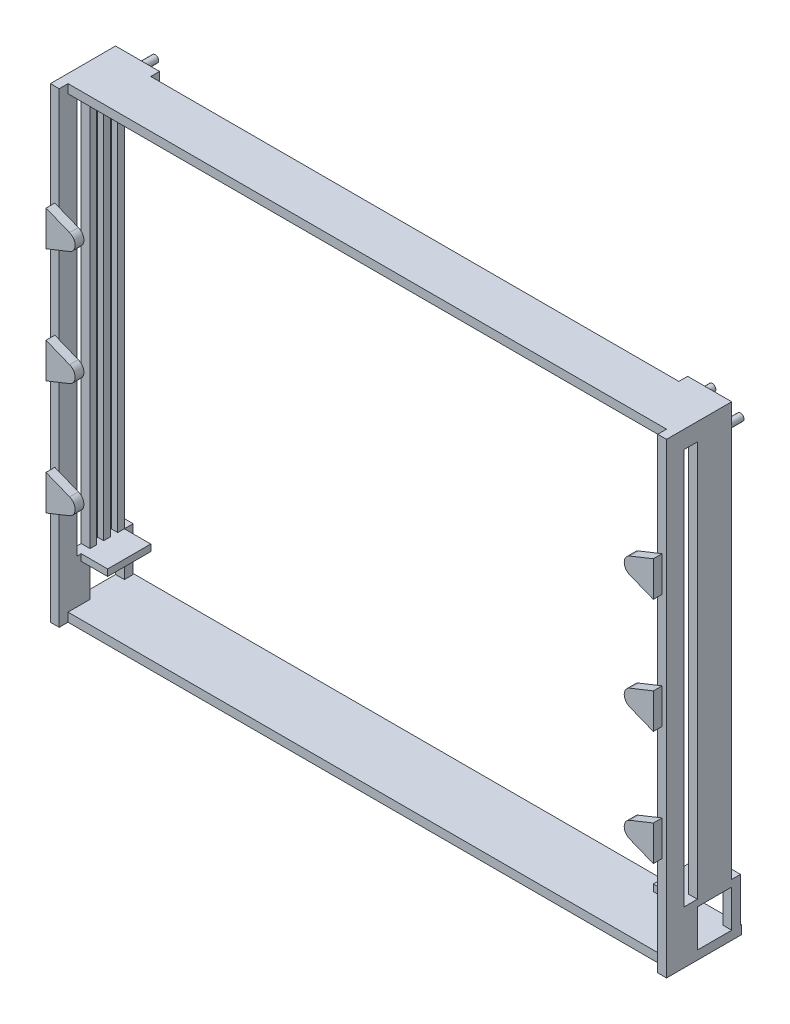
SolidWorks part; units mm, degrees
ref_plane "Plan de face" through (0, 0, 0) normal (0, 0, 1) x (1, 0, 0)
ref_plane "Plan de dessus" through (0, 0, 0) normal (0, 1, 0) x (1, 0, 0)
ref_plane "Plan de droite" through (0, 0, 0) normal (1, 0, 0) x (0, 0, -1)
sketch "Esquisse1" plane through (0, 0, 0) normal (0, 1, 0) x (1, 0, 0)
  line L0 (10, 0) -> (690, 0) construction
  line L1 (0, 0) -> (10, 0)
  line L2 (0, 0) -> (0, 25)
  line L3 (0, 25) -> (10, 25)
  line L4 (10, 0) -> (10, 25)
  line L6 (690, 0) -> (700, 0)
  line L7 (690, 0) -> (690, 25)
  line L8 (690, 25) -> (700, 25)
  line L9 (700, 0) -> (700, 25)
  dimension "D1" = 680
  dimension "D2" = 10
  dimension "D3" = 25
  dimension "D4" = 10
  dimension "D5" = 25
extrude "Boss.-Extru.1" add sketch "Esquisse1" along normal blind 530
sketch "Esquisse7" plane through (0, 0, 0) normal (0, 0, 1) x (1, 0, 0)
  line L0 (5, 530) -> (5, 415) construction
  line L1 (0, 530) -> (10, 530) construction
  line L2 (5, 415) -> (5, 375) construction
  line L3 (5, 375) -> (5, 285) construction
  line L4 (5, 415) -> (55, 395)
  line L5 (55, 395) -> (5, 375)
  line L6 (5, 375) -> (5, 415)
  line L7 (5, 285) -> (5, 245) construction
  line L8 (5, 245) -> (5, 155) construction
  line L9 (5, 155) -> (5, 115) construction
  line L10 (615, 395) -> (5, 395) construction
  line L11 (5, 285) -> (55, 265)
  line L12 (55, 265) -> (5, 245)
  line L13 (5, 245) -> (5, 285)
  line L14 (5, 155) -> (55, 135)
  line L15 (55, 135) -> (5, 115)
  line L16 (5, 115) -> (5, 155)
  line L17 (615, 460) -> (615, 330) construction
  line L18 (615, 330) -> (615, 200) construction
  line L19 (615, 265) -> (5, 265) construction
  line L20 (615, 200) -> (615, 70) construction
  line L21 (615, 135) -> (5, 135) construction
  line L23 (10, 530) -> (690, 530) construction
  line L24 (350, 530) -> (350, 0) construction
  line L25 (85, 135) -> (695, 135) construction
  line L26 (85, 265) -> (695, 265) construction
  line L27 (85, 330) -> (85, 200) construction
  line L28 (85, 395) -> (695, 395) construction
  line L29 (695, 155) -> (695, 115) construction
  line L30 (695, 245) -> (695, 155) construction
  line L31 (695, 285) -> (695, 245) construction
  line L32 (695, 375) -> (695, 285) construction
  line L33 (695, 415) -> (695, 375) construction
  line L34 (695, 115) -> (695, 155)
  line L35 (645, 135) -> (695, 115)
  line L36 (695, 155) -> (645, 135)
  line L37 (695, 245) -> (695, 285)
  line L38 (645, 265) -> (695, 245)
  line L39 (695, 285) -> (645, 265)
  line L40 (695, 375) -> (695, 415)
  line L41 (645, 395) -> (695, 375)
  line L42 (695, 415) -> (645, 395)
  dimension "D1" = 20
  dimension "D2" = 50
  dimension "D3" = 20
  dimension "D4" = 20
  dimension "D5" = 20
  dimension "D6" = 50
  dimension "D7" = 20
  dimension "D8" = 20
  dimension "D9" = 50
extrude "Boss.-Extru.4" add sketch "Esquisse7" along normal blind 10
sketch "Esquisse8" plane through (0, 0, -25) normal (0, 0, -1) x (-1, 0, 0)
  line L0 (-10, 530) -> (-10, 0) construction
  line L1 (0, 0) -> (-10, 0)
  line L2 (0, 0) -> (0, 10)
  line L3 (0, 10) -> (-10, 10)
  line L4 (-10, 0) -> (-10, 10)
  dimension "D1" = 10
extrude "Boss.-Extru.5" add sketch "Esquisse8" along normal blind 60
sketch "Esquisse9" plane through (10, 0, 0) normal (1, 0, 0) x (0, 0, -1)
  line L0 (0, 0) -> (85, 0) construction
  line L1 (85, 10) -> (25, 10)
  line L2 (85, 10) -> (85, 0)
  line L3 (85, 0) -> (25, 0)
  line L4 (25, 10) -> (25, 0)
  line L5 (25, 530) -> (25, 0) construction
extrude "Boss.-Extru.6" add sketch "Esquisse9" along normal blind 690
fillet "Congé1" radius 10 3 edges at (55, 395, 5) (55, 135, 5) (55, 265, 5)
fillet "Congé2" radius 10 1 edges at (645, 395, 5)
fillet "Congé3" radius 10 1 edges at (645, 265, 5)
fillet "Congé4" radius 10 1 edges at (645, 135, 5)
sketch "Esquisse10" plane through (0, 0, -25) normal (0, 0, 1) x (1, 0, 0)
  line L1 (10, 0) -> (690, 0)
  line L2 (10, 0) -> (10, 10)
  line L3 (10, 10) -> (690, 10)
  line L4 (690, 0) -> (690, 10)
extrude "Boss.-Extru.7" add sketch "Esquisse10" along normal blind 15
sketch "Esquisse11" plane through (0, 0, -25) normal (0, 0, -1) x (-1, 0, 0)
  line L0 (-690, 530) -> (-690, 10) construction
  line L1 (-700, 10) -> (-690, 10)
  line L2 (-700, 10) -> (-700, 60)
  line L3 (-700, 60) -> (-690, 60)
  line L4 (-690, 10) -> (-690, 60)
  line L5 (-350, 10) -> (-350, 457.7325) construction
  line L6 (-700, 10) -> (0, 10) construction
  line L7 (0, 60) -> (-10, 60)
  line L8 (-10, 10) -> (-10, 60)
  line L9 (0, 10) -> (-10, 10)
  line L10 (0, 10) -> (0, 60)
  dimension "D1" = 50
extrude "Boss.-Extru.8" add sketch "Esquisse11" along normal blind 10
sketch "Esquisse12" plane through (0, 0, -35) normal (0, 0, -1) x (-1, 0, 0)
  line L0 (-690, 10) -> (-690, 60) construction
  line L1 (-700, 60) -> (-690, 60)
  line L2 (-700, 60) -> (-700, 52.5)
  line L3 (-700, 52.5) -> (-690, 52.5)
  line L4 (-690, 60) -> (-690, 52.5)
  line L5 (-350, 10) -> (-350, 481.8712) construction
  line L6 (-700, 10) -> (0, 10) construction
  line L11 (-10, 60) -> (-10, 52.5)
  line L12 (0, 52.5) -> (-10, 52.5)
  line L13 (0, 60) -> (0, 52.5)
  line L14 (0, 60) -> (-10, 60)
  dimension "D1" = 7.5
extrude "Boss.-Extru.9" add sketch "Esquisse12" along normal blind 39
sketch "Esquisse13" plane through (690, 0, 0) normal (-1, 0, 0) x (0, 0, 1)
  line L1 (-25, 60) -> (-74, 60)
  line L2 (-25, 60) -> (-25, 52.5)
  line L3 (-25, 52.5) -> (-74, 52.5)
  line L4 (-74, 60) -> (-74, 52.5)
extrude "Boss.-Extru.10" add sketch "Esquisse13" along normal blind 30
sketch "Esquisse19" plane through (10, 0, 0) normal (1, 0, 0) x (0, 0, -1)
  line L1 (25, 60) -> (74, 60)
  line L2 (25, 60) -> (25, 52.5)
  line L3 (25, 52.5) -> (74, 52.5)
  line L4 (74, 60) -> (74, 52.5)
extrude "Boss.-Extru.14" add sketch "Esquisse19" along normal blind 30
sketch "Esquisse14" plane through (0, 60, 0) normal (0, 1, 0) x (1, 0, 0)
  line L0 (350, 85) -> (350, -100.166) construction
  line L1 (690, 25) -> (700, 25)
  line L2 (690, 25) -> (690, 74)
  line L3 (690, 74) -> (700, 74)
  line L4 (700, 25) -> (700, 74)
  line L5 (700, 85) -> (0, 85) construction
  line L6 (0, 25) -> (0, 74)
  line L7 (10, 74) -> (0, 74)
  line L8 (10, 25) -> (10, 74)
  line L9 (10, 25) -> (0, 25)
extrude "Boss.-Extru.11" add sketch "Esquisse14" along normal blind 470
sketch "Esquisse16" plane through (690, 0, 0) normal (-1, 0, 0) x (0, 0, 1)
  line L1 (-74, 530) -> (-64, 530)
  line L2 (-74, 530) -> (-74, 520)
  line L3 (-74, 520) -> (-64, 520)
  line L4 (-64, 530) -> (-64, 520)
  dimension "D1" = 10
  dimension "D2" = 10
extrude "Boss.-Extru.12" add sketch "Esquisse16" along normal blind 20
sketch "Esquisse20" plane through (10, 0, 0) normal (1, 0, 0) x (0, 0, -1)
  line L1 (74, 530) -> (64, 530)
  line L2 (74, 530) -> (74, 520)
  line L3 (74, 520) -> (64, 520)
  line L4 (64, 530) -> (64, 520)
  dimension "D1" = 10
  dimension "D2" = 10
extrude "Boss.-Extru.15" add sketch "Esquisse20" along normal blind 20
sketch "Esquisse21" plane through (10, 0, 0) normal (1, 0, 0) x (0, 0, -1)
  line L0 (0, 530) -> (64, 530) construction
  line L1 (64, 520) -> (10, 520)
  line L2 (64, 520) -> (64, 530)
  line L3 (64, 530) -> (10, 530)
  line L4 (10, 520) -> (10, 530)
  dimension "D1" = 54
extrude "Boss.-Extru.16" add sketch "Esquisse21" along normal up to next
sketch "Esquisse22" plane through (690, 0, 0) normal (-1, 0, 0) x (0, 0, 1)
  line L0 (-74, 530) -> (-20, 530) construction
  line L1 (-74, 530) -> (0, 530) construction
  line L2 (-20, 530) -> (-20, 0) construction
  line L3 (-85, 0) -> (0, 0) construction
  line L4 (-20, 510) -> (-35, 510) construction
  line L5 (-35, 510) -> (-35, 530) construction
  line L8 (-35, 510) -> (-20, 510)
  line L9 (-35, 510) -> (-35, 60)
  line L10 (-35, 60) -> (-20, 60)
  line L11 (-20, 510) -> (-20, 60)
  dimension "D1" = 54
  dimension "D2" = 15
  dimension "D3" = 20
  dimension "D4" = 450
extrude "Enlèv. mat.-Extru.1" cut sketch "Esquisse22" against normal through all both and the other way through all
sketch "Esquisse23" plane through (0, 0, -74) normal (0, 0, -1) x (-1, 0, 0)
  line L1 (-700, 52.5) -> (-690, 52.5)
  line L2 (-700, 52.5) -> (-700, 60)
  line L3 (-700, 60) -> (-690, 60)
  line L4 (-690, 52.5) -> (-690, 60)
extrude "Boss.-Extru.17" add sketch "Esquisse23" along normal blind 10
sketch "Esquisse24" plane through (0, 52.5, 0) normal (0, -1, 0) x (1, 0, 0)
  line L1 (690, -74) -> (700, -74)
  line L2 (690, -74) -> (690, -84)
  line L3 (690, -84) -> (700, -84)
  line L4 (700, -74) -> (700, -84)
extrude "Boss.-Extru.18" add sketch "Esquisse24" along normal through all contours L2 L1 L4 L3
sketch "Esquisse25" plane through (0, 0, -74) normal (0, 0, -1) x (-1, 0, 0)
  line L1 (-10, 60) -> (0, 60)
  line L2 (-10, 60) -> (-10, 52.5)
  line L3 (-10, 52.5) -> (0, 52.5)
  line L4 (0, 60) -> (0, 52.5)
extrude "Boss.-Extru.19" add sketch "Esquisse25" along normal blind 10
sketch "Esquisse26" plane through (0, 52.5, 0) normal (0, -1, 0) x (1, 0, 0)
  line L1 (10, -74) -> (0, -74)
  line L2 (10, -74) -> (10, -84)
  line L3 (10, -84) -> (0, -84)
  line L4 (0, -74) -> (0, -84)
extrude "Boss.-Extru.20" add sketch "Esquisse26" along normal through all
sketch "Esquisse28" plane through (690, 0, 0) normal (-1, 0, 0) x (0, 0, 1)
  line L0 (-35, 510) -> (-42.5, 510) construction
  line L1 (-42.5, 510) -> (-50.5, 510) construction
  line L2 (-50.5, 510) -> (-58.5, 510) construction
  line L3 (-58.5, 510) -> (-66.5, 510) construction
  line L4 (-66.5, 510) -> (-74, 510) construction
  line L5 (-74, 60) -> (-74, 530) construction
  line L6 (-35, 60) -> (-74, 60) construction
  line L8 (-66.5, 510) -> (-58.5, 510)
  line L9 (-66.5, 510) -> (-66.5, 60)
  line L10 (-66.5, 60) -> (-58.5, 60)
  line L11 (-58.5, 510) -> (-58.5, 60)
  line L12 (-50.5, 60) -> (-42.5, 60)
  line L13 (-50.5, 60) -> (-50.5, 510)
  line L14 (-50.5, 510) -> (-42.5, 510)
  line L15 (-42.5, 60) -> (-42.5, 510)
  dimension "D1" = 7.5
  dimension "D2" = 8
  dimension "D3" = 8
  dimension "D4" = 7.5
extrude "Enlèv. mat.-Extru.2" cut sketch "Esquisse28" against normal blind 7
sketch "Esquisse29" plane through (10, 0, 0) normal (1, 0, 0) x (0, 0, -1)
  line L0 (35, 510) -> (42.5, 510) construction
  line L1 (42.5, 510) -> (50.5, 510) construction
  line L2 (50.5, 510) -> (58.5, 510) construction
  line L3 (58.5, 510) -> (66.5, 510) construction
  line L4 (66.5, 510) -> (74, 510) construction
  line L5 (74, 530) -> (74, 60) construction
  line L6 (35, 60) -> (74, 60) construction
  line L8 (42.5, 60) -> (50.5, 60)
  line L9 (42.5, 60) -> (42.5, 510)
  line L10 (42.5, 510) -> (50.5, 510)
  line L11 (50.5, 60) -> (50.5, 510)
  line L12 (58.5, 510) -> (66.5, 510)
  line L13 (58.5, 510) -> (58.5, 60)
  line L14 (58.5, 60) -> (66.5, 60)
  line L15 (66.5, 510) -> (66.5, 60)
  dimension "D1" = 7.5
  dimension "D2" = 8
  dimension "D3" = 7.5
  dimension "D4" = 8
extrude "Enlèv. mat.-Extru.3" cut sketch "Esquisse29" against normal blind 7
sketch "Esquisse31" plane through (0, 0, -64) normal (0, 0, -1) x (-1, 0, 0)
  line L0 (-670, 530) -> (-30, 530) construction
  line L1 (-670, 520) -> (-650, 520)
  line L2 (-670, 520) -> (-670, 530)
  line L3 (-670, 530) -> (-650, 530)
  line L4 (-650, 520) -> (-650, 530)
  line L6 (-30, 520) -> (-50, 520)
  line L7 (-30, 520) -> (-30, 530)
  line L8 (-30, 530) -> (-50, 530)
  line L9 (-50, 520) -> (-50, 530)
  dimension "D1" = 20
  dimension "D2" = 20
extrude "Boss.-Extru.22" add sketch "Esquisse31" along normal blind 10
sketch "Esquisse33" plane through (0, 0, -74) normal (0, 0, -1) x (-1, 0, 0)
  line L3 (-700, 525) -> (-670, 525) construction
  line L6 (-700, 530) -> (-700, 60) construction
  circle A0 centre (-670, 525) radius 4
  dimension "D2" = 8
  dimension "D1" = 30
extrude "Boss.-Extru.23" add sketch "Esquisse33" along normal blind 8
sketch "Esquisse34" plane through (0, 0, -74) normal (0, 0, -1) x (-1, 0, 0)
  line L3 (-700, 530) -> (-650, 530) construction
  line L4 (-695, 530) -> (-695, 505) construction
  circle A0 centre (-695, 505) radius 4
  dimension "D2" = 8
  dimension "D1" = 25
extrude "Boss.-Extru.24" add sketch "Esquisse34" along normal blind 15
sketch "Esquisse35" plane through (0, 0, -74) normal (0, 0, -1) x (-1, 0, 0)
  line L5 (0, 60) -> (0, 530) construction
  line L6 (0, 525) -> (-30, 525) construction
  circle A0 centre (-30, 525) radius 4
  dimension "D2" = 8
  dimension "D1" = 30
extrude "Boss.-Extru.25" add sketch "Esquisse35" along normal blind 15
sketch "Esquisse36" plane through (0, 0, -74) normal (0, 0, -1) x (-1, 0, 0)
  line L4 (-5, 505) -> (-5, 530) construction
  line L5 (-50, 530) -> (0, 530) construction
  circle A0 centre (-5, 505) radius 4
  dimension "D2" = 8
  dimension "D1" = 25
extrude "Boss.-Extru.26" add sketch "Esquisse36" along normal blind 8
equation "\".47.00cm\"=47"
